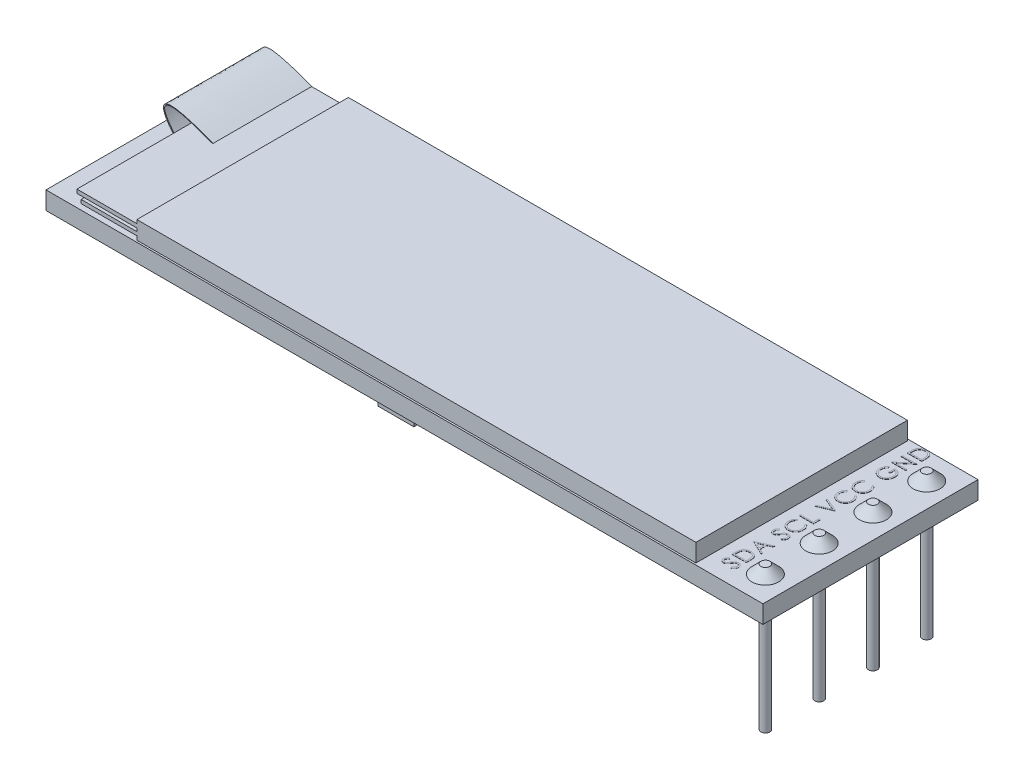
SolidWorks part; units mm, degrees
ref_plane "Front Plane" through (0, 0, 0) normal (0, 0, 1) x (1, 0, 0)
ref_plane "Top Plane" through (0, 0, 0) normal (0, 1, 0) x (1, 0, 0)
ref_plane "Right Plane" through (0, 0, 0) normal (1, 0, 0) x (0, 0, -1)
sketch "Sketch1" plane through (0, 0, 0) normal (0, 1, 0) x (1, 0, 0)
  line L1 (0, 0) -> (40, 0)
  line L2 (0, 0) -> (0, -12)
  line L3 (0, -12) -> (40, -12)
  line L4 (40, 0) -> (40, -12)
  dimension "D1" = 12
  dimension "D2" = 40
extrude "Boss-Extrude1" add sketch "Sketch1" along normal blind 1
sketch "Sketch2" plane through (0, 1, 0) normal (0, 1, 0) x (1, 0, 0)
  line L0 (0, -12) -> (40, -12) construction
  line L1 (4.9697, -0.1) -> (36.1613, -0.1)
  line L2 (4.9697, -0.1) -> (4.9697, -11.9)
  line L3 (4.9697, -11.9) -> (36.1613, -11.9)
  line L4 (36.1613, -0.1) -> (36.1613, -11.9)
  line L5 (40, 0) -> (0, 0) construction
  dimension "D1" = 0.1
  dimension "D2" = 0.1
extrude "Boss-Extrude3" add sketch "Sketch2" along normal blind 1
sketch "Sketch3" plane through (0, 0, 11.9) normal (0, 0, 1) x (1, 0, 0)
  line L1 (4.9697, 1.2145) -> (1.8634, 1.2145)
  line L2 (4.9697, 2) -> (4.9697, 1) construction
  line L3 (1.8634, 1.2145) -> (1.8634, 1.4193)
  line L4 (1.8634, 1.4193) -> (4.9697, 1.4193)
  line L5 (4.9697, 1.2145) -> (4.9697, 1.4193)
  line L6 (4.9697, 1.5908) -> (1.6259, 1.5908)
  line L7 (1.6259, 1.5908) -> (1.6259, 1.8019)
  line L8 (1.6259, 1.8019) -> (4.9697, 1.8019)
  line L9 (4.9697, 1.8019) -> (4.9697, 1.5908)
extrude "Boss-Extrude4" add sketch "Sketch3" against normal blind 11.5
sketch "Sketch4" plane through (0, 0, 0.4) normal (0, 0, -1) x (-1, 0, 0)
  line L1 (-4.9697, 1.8019) -> (-1.6259, 1.8019) construction
  line L2 (-40, 1) -> (0, 1) construction
  line L3 (-3.2199, 1.8019) -> (-3.1345, 1.8019)
  line L4 (-1.2333, 1) -> (-1.1242, 1)
  spline S0 degree 2 poles (-3.1345, 1.8019) (0.8493, 3.3592) (-1.2333, 1) knots 0 0 0 1 1 1
  spline S1 degree 2 poles (-3.2199, 1.8019) (0.9087, 3.4366) (-1.1242, 1) knots 0 0 0 1 1 1
extrude "Boss-Extrude5" add sketch "Sketch4" against normal blind 5.5
sketch "Sketch5" plane through (0, 1, 0) normal (0, 1, 0) x (1, 0, 0)
  line L0 (0, -12) -> (40, -12) construction
  line L1 (40, 0) -> (0, 0) construction
  circle A0 centre (38.6385, -1.5) radius 0.75
  circle A1 centre (38.6385, -10.5) radius 0.75
  circle A2 centre (38.6385, -4.5) radius 0.75
  circle A3 centre (38.6385, -7.5) radius 0.75
  dimension "D1" = 1.5
  dimension "D2" = 1.5
  dimension "D3" = 1.5
  dimension "D4" = 1.5
  dimension "D5" = 1.5
  dimension "D6" = 1.5
  dimension "D7" = 3
  dimension "D8" = 3
extrude "Boss-Extrude6" add sketch "Sketch5" along normal blind 0.5
chamfer "Chamfer1" distance 0.5 angle 45 4 edges at (38.6385, 1.5, 2.25) (38.6385, 1.5, 5.25) (38.6385, 1.5, 8.25) (38.6385, 1.5, 11.25)
sketch "Sketch6" plane through (0, 1.5, 0) normal (0, 1, 0) x (1, 0, 0)
  circle A0 centre (38.6385, -10.5) radius 0.25
  circle A1 centre (38.6385, -7.5) radius 0.25
  circle A2 centre (38.6385, -4.5) radius 0.25
  circle A3 centre (38.6385, -1.5) radius 0.25
extrude "Boss-Extrude7" add sketch "Sketch6" against normal blind 8
sketch "Sketch7" plane through (0, 0, 0) normal (0, -1, 0) x (1, 0, 0)
  line L1 (31.0979, 6.3498) -> (32.5979, 6.3498)
  line L2 (31.0979, 6.3498) -> (31.0979, 3.1498)
  line L3 (31.0979, 3.1498) -> (32.5979, 3.1498)
  line L4 (32.5979, 6.3498) -> (32.5979, 3.1498)
  dimension "D1" = 1.5
  dimension "D2" = 3.2
extrude "Boss-Extrude8" add sketch "Sketch7" along normal blind 1
sketch "Sketch8" plane through (0, 0, 0) normal (0, -1, 0) x (-1, 0, 0)
  line L0 (-17.7138, -2.7891) -> (-19.7138, -2.7891)
  line L1 (-17.7138, -1.3891) -> (-19.7138, -1.3891)
  line L2 (-17.7138, -1.3891) -> (-17.7138, -0.5891)
  line L3 (-17.7138, -0.5891) -> (-19.7138, -0.5891)
  line L4 (-19.7138, -1.3891) -> (-19.7138, -0.5891)
  line L5 (-17.7138, -2.7891) -> (-17.7138, -1.9891)
  line L6 (-19.7138, -2.7891) -> (-19.7138, -1.9891)
  line L7 (-17.7138, -1.9891) -> (-19.7138, -1.9891)
  line L8 (-17.7138, -4.1891) -> (-19.7138, -4.1891)
  line L9 (-17.7138, -4.1891) -> (-17.7138, -3.3891)
  line L10 (-19.7138, -4.1891) -> (-19.7138, -3.3891)
  line L11 (-17.7138, -3.3891) -> (-19.7138, -3.3891)
  line L12 (-17.7138, -5.5891) -> (-19.7138, -5.5891)
  line L13 (-17.7138, -5.5891) -> (-17.7138, -4.7891)
  line L14 (-19.7138, -5.5891) -> (-19.7138, -4.7891)
  line L15 (-17.7138, -4.7891) -> (-19.7138, -4.7891)
  line L16 (-17.7138, -6.9891) -> (-19.7138, -6.9891)
  line L17 (-17.7138, -6.9891) -> (-17.7138, -6.1891)
  line L18 (-19.7138, -6.9891) -> (-19.7138, -6.1891)
  line L19 (-17.7138, -6.1891) -> (-19.7138, -6.1891)
  line L20 (-17.7138, -8.3891) -> (-19.7138, -8.3891)
  line L21 (-17.7138, -8.3891) -> (-17.7138, -7.5891)
  line L22 (-19.7138, -8.3891) -> (-19.7138, -7.5891)
  line L23 (-17.7138, -7.5891) -> (-19.7138, -7.5891)
  line L24 (-17.7138, -9.7891) -> (-19.7138, -9.7891)
  line L25 (-17.7138, -9.7891) -> (-17.7138, -8.9891)
  line L26 (-19.7138, -9.7891) -> (-19.7138, -8.9891)
  line L27 (-17.7138, -8.9891) -> (-19.7138, -8.9891)
  line L28 (-17.7138, -11.1891) -> (-19.7138, -11.1891)
  line L29 (-17.7138, -11.1891) -> (-17.7138, -10.3891)
  line L30 (-19.7138, -11.1891) -> (-19.7138, -10.3891)
  line L31 (-17.7138, -10.3891) -> (-19.7138, -10.3891)
  line L32 (-25.3795, -4.0891) -> (-27.3795, -4.0891)
  line L33 (-25.3795, -1.9891) -> (-27.3795, -1.9891)
  line L34 (-25.3795, -1.9891) -> (-25.3795, -2.7891)
  line L35 (-25.3795, -2.7891) -> (-27.3795, -2.7891)
  line L36 (-27.3795, -1.9891) -> (-27.3795, -2.7891)
  line L37 (-25.3795, -3.2891) -> (-25.3795, -4.0891)
  line L38 (-27.3795, -3.2891) -> (-27.3795, -4.0891)
  line L39 (-25.3795, -3.2891) -> (-27.3795, -3.2891)
  line L40 (-25.3795, -5.3891) -> (-27.3795, -5.3891)
  line L41 (-25.3795, -4.5891) -> (-25.3795, -5.3891)
  line L42 (-27.3795, -4.5891) -> (-27.3795, -5.3891)
  line L43 (-25.3795, -4.5891) -> (-27.3795, -4.5891)
  line L44 (-25.3795, -6.6891) -> (-27.3795, -6.6891)
  line L45 (-25.3795, -5.8891) -> (-25.3795, -6.6891)
  line L46 (-27.3795, -5.8891) -> (-27.3795, -6.6891)
  line L47 (-25.3795, -5.8891) -> (-27.3795, -5.8891)
  line L48 (-25.3795, -7.9891) -> (-27.3795, -7.9891)
  line L49 (-25.3795, -7.1891) -> (-25.3795, -7.9891)
  line L50 (-27.3795, -7.1891) -> (-27.3795, -7.9891)
  line L51 (-25.3795, -7.1891) -> (-27.3795, -7.1891)
  dimension "D1" = 0.8
  dimension "D2" = 2
  dimension "D4" = 2
  dimension "D3" = 8
  dimension "D5" = 5
extrude "Boss-Extrude9" add sketch "Sketch8" along normal blind 1
sketch "Sketch9" plane through (0, 1, 0) normal (0, 1, 0) x (1, 0, 0)
  text T0 "SDA SCL VCC GND" font "Century Gothic" height 0.8
extrude "Boss-Extrude10" add sketch "Sketch9" along normal blind 0.01
